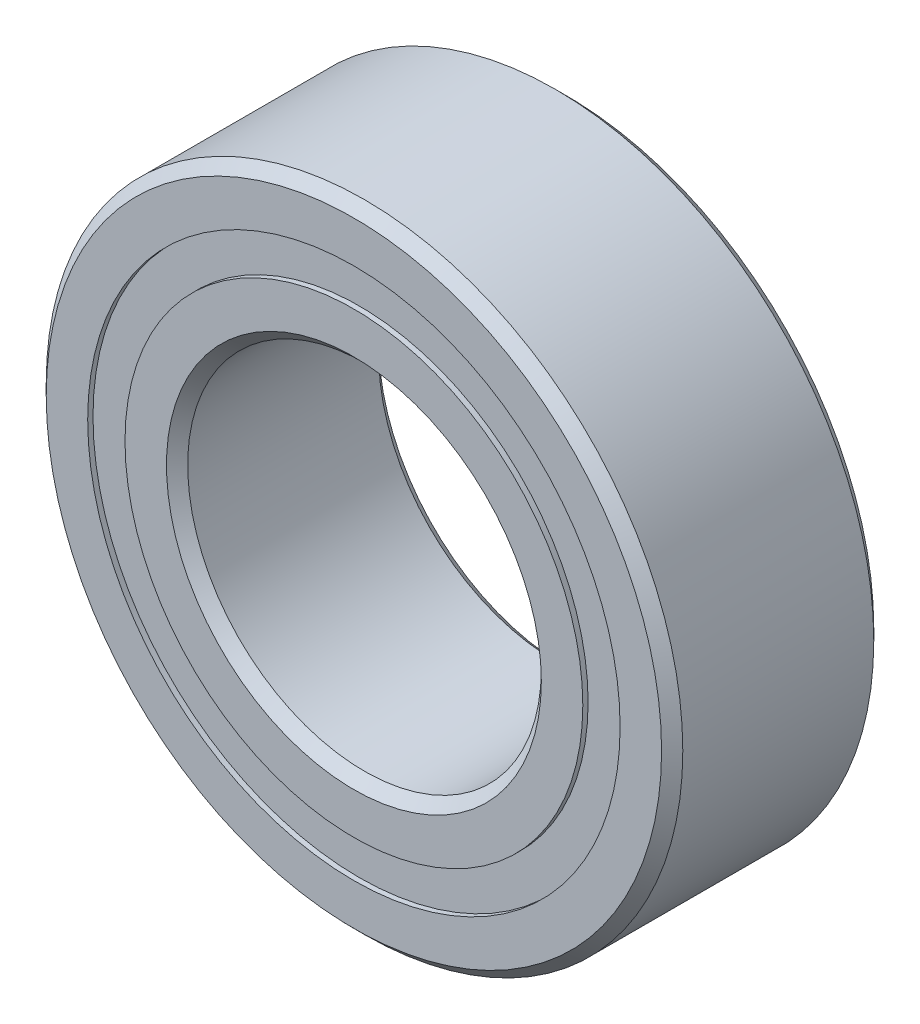
SolidWorks part; units mm, degrees
ref_plane "Front Plane" through (0, 0, 0) normal (0, 0, 1) x (1, 0, 0)
ref_plane "Top Plane" through (0, 0, 0) normal (0, 1, 0) x (1, 0, 0)
ref_plane "Right Plane" through (0, 0, 0) normal (1, 0, 0) x (0, 0, -1)
sketch "Sketch1" plane through (0, 0, 0) normal (1, 0, 0) x (0, 0, -1)
  line L0 (-1.5, 0) -> (1.5, 0) construction
  line L1 (0, 4.5) -> (0, -4.5) construction
  line L2 (1.35, 4.5) -> (-1.35, 4.5)
  line L3 (-1.35, 4.5) -> (-1.5, 4.35)
  line L4 (-1.5, 4.35) -> (-1.5, 3.7637)
  line L5 (-1.5, 3.7637) -> (-0.6667, 3.7637)
  line L6 (1.5, 3.7637) -> (0.6667, 3.7637)
  line L7 (1.5, 4.35) -> (1.5, 3.7637)
  line L8 (1.35, 4.5) -> (1.5, 4.35)
  line L9 (0, 4.5) -> (0, 3.5) construction
  line L10 (0, 3.5) -> (0, 2.5) construction
  arc A0 (-0.6667, 3.7637) -> (0.6667, 3.7637) centre (0, 3.5) cw
  point P14 (0, 2.5)
  dimension "Width" = 3
  dimension "OD" = 9
  dimension "D1" = 45
  dimension "D2" = 0.15
  dimension "Shaft Dia" = 5
  dimension "D3" = 1.3333
  dimension "D4" = 0.2637
revolve "Revolve1" add sketch "Sketch1" angle 360 about L0
sketch "Sketch3" plane through (0, 0, 0) normal (1, 0, 0) x (0, 0, -1)
  line L0 (-1.5, 3.2363) -> (-0.6667, 3.2363)
  line L1 (0, 4.5) -> (0, -4.5) construction
  line L2 (-1.5, 4.35) -> (-1.5, 3.7637) construction
  line L3 (-1.5, 3.2363) -> (-1.5, 2.65)
  line L4 (-1.35, 4.5) -> (-1.5, 4.35) construction
  line L5 (-1.5, 2.65) -> (-1.35, 2.5)
  line L6 (-1.35, 2.5) -> (1.35, 2.5)
  line L7 (1.35, 4.5) -> (1.35, -4.5) construction
  line L8 (1.35, 2.5) -> (1.5, 2.65)
  line L9 (1.5, -4.35) -> (1.5, 4.35) construction
  line L10 (1.5, 2.65) -> (1.5, 3.2363)
  line L11 (1.5, 3.2363) -> (0.6667, 3.2363)
  line L13 (1.35, 4.5) -> (1.5, 4.35) construction
  arc A0 (0.6667, 3.7637) -> (-0.6667, 3.7637) centre (0, 3.5) ccw construction
  arc A1 (0.6667, 3.2363) -> (-0.6667, 3.2363) centre (0, 3.5) cw
revolve "Revolve3" add sketch "Sketch3" angle 360 about L0
sketch "Sketch4" plane through (0, 0, 0) normal (1, 0, 0) x (0, 0, -1)
  line L0 (-0.7169, 3.5) -> (0.7169, 3.5)
  arc A2 (-0.7169, 3.5) -> (0.7169, 3.5) centre (0, 3.5) cw
  arc A3 (0.6667, 3.7637) -> (-0.6667, 3.7637) centre (0, 3.5) ccw construction
revolve "Revolve4" add sketch "Sketch4" angle 360 about L0
ref_axis "Axis1" through (0, 0, -1.5) along (0, 0, 1)
pattern_circular "CirPattern1" count 12 every 30 about axis through (0, 0, -1.5) along (0, 0, 1) of bodies 104
sketch "Sketch5" plane through (0, 0, 0) normal (1, 0, 0) x (0, 0, -1)
  line L0 (-1.5, 3.7637) -> (-0.6667, 3.7637) construction
  line L1 (-1.425, 3.7637) -> (-0.7169, 3.7637)
  line L2 (-1.425, 3.7637) -> (-1.425, 3.2363)
  line L3 (-1.425, 3.2363) -> (-0.7169, 3.2363)
  line L4 (-0.7169, 3.7637) -> (-0.7169, 3.2363)
  line L5 (-1.5, 3.2363) -> (-0.6667, 3.2363) construction
  line L6 (1.5, 3.7637) -> (0.6667, 3.7637) construction
  line L7 (1.425, 3.7637) -> (0.7169, 3.7637)
  line L8 (1.425, 3.7637) -> (1.425, 3.2363)
  line L9 (1.425, 3.2363) -> (0.7169, 3.2363)
  line L10 (0.7169, 3.7637) -> (0.7169, 3.2363)
  line L11 (1.5, 3.2363) -> (0.6667, 3.2363) construction
  line L12 (-1.35, 4.5) -> (-1.5, 4.35) construction
  point P18 (-1.425, 4.425)
revolve "Revolve5" add sketch "Sketch5" angle 360 about L0
sketch "Sketch6" plane through (0, 0, 0) normal (1, 0, 0) x (0, 0, -1)
  line L0 (1.5, 0) -> (-1.5, 0) construction
  line L1 (1.5, 3.7637) -> (0.7126, 3.7637)
  line L2 (1.5, 3.7637) -> (1.5, 6.9469)
  line L3 (1.5, 6.9469) -> (0.7126, 6.9469)
  line L4 (0.7126, 3.7637) -> (0.7126, 6.9469)
  dimension "Th" = 0.7874
  dimension "Flange OD" = 13.8938
revolve "Revolve6" [suppressed] add sketch "Sketch6" angle 360 about L0
equation "\"D2@Sketch1\" = \"Width@Sketch1\"*.05"
equation "\"D3@Sketch1\" = \"Width@Sketch1\"/2.25"
equation "\"D4@Sketch1\" = (((\"OD@Sketch1\"-\"Width@Sketch1\")/2)/3.25)/3.5"
equation "\"D2@CirPattern1\" = 360/\"Balls@CirPattern1\""
